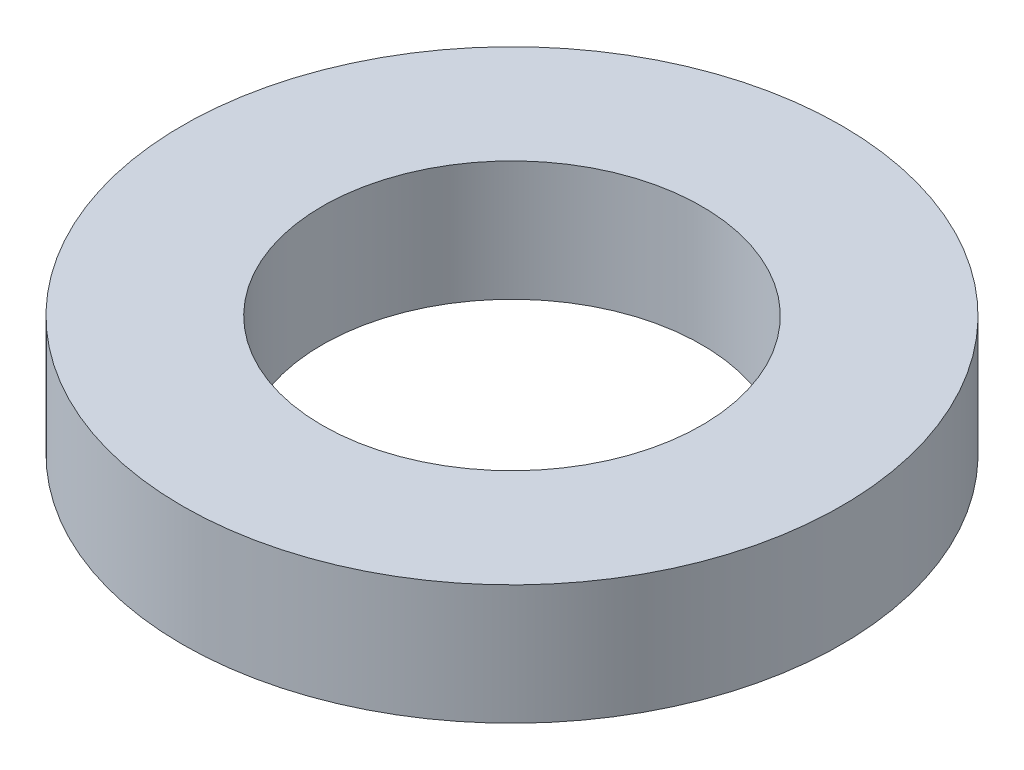
SolidWorks part; units mm, degrees
ref_plane "Front Plane" through (0, 0, 0) normal (0, 0, 1) x (1, 0, 0)
ref_plane "Top Plane" through (0, 0, 0) normal (0, 1, 0) x (1, 0, 0)
ref_plane "Right Plane" through (0, 0, 0) normal (1, 0, 0) x (0, 0, -1)
sketch "Sketch1" plane through (0, 0, 0) normal (0, 1, 0) x (1, 0, 0)
  circle A0 centre (0, 0) radius 82.5
  dimension "FLANGE_OD" = 165
extrude "Boss-Extrude1" add sketch "Sketch1" along normal blind 30
sketch "Sketch2" plane through (0, 0, 0) normal (0, 1, 0) x (1, 0, 0)
  circle A0 centre (0, 0) radius 47.5
  dimension "BORE_D" = 95
extrude "Cut-Extrude1" cut sketch "Sketch2" along normal through all
sketch "Sketch3" plane through (0, 30, 0) normal (0, 1, 0) x (1, 0, 0)
  circle A0 centre (0, 0) radius 33.8101 construction
  circle A1 centre (-33.8101, 0) radius 4.9413
  dimension "BOLT_D" = 9.8826
  dimension "BOLT_PCD" = 67.6201
extrude "Cut-Extrude2" cut sketch "Sketch3" against normal blind 26.8039 rebuild error yes
pattern_circular "CirPattern1" count 8 over 360 rebuild error yes
